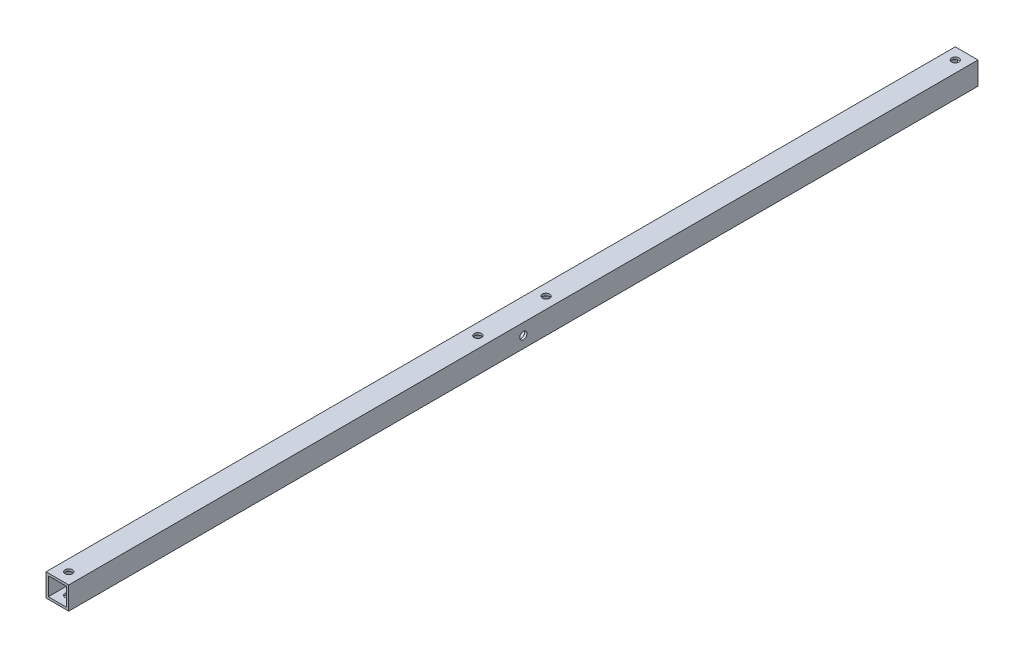
SolidWorks part; units mm, degrees
ref_plane "正面" through (0, 0, 0) normal (0, 0, 1) x (1, 0, 0)
ref_plane "平面" through (0, 0, 0) normal (0, 1, 0) x (1, 0, 0)
ref_plane "右側面" through (0, 0, 0) normal (1, 0, 0) x (0, 0, -1)
sketch "ｽｹｯﾁ1" plane through (0, 0, 0) normal (0, 0, 1) x (1, 0, 0)
  line L0 (-4, 4) -> (-4, -4)
  line L1 (-5, 5) -> (5, 5)
  line L2 (-5, 5) -> (-5, -5)
  line L3 (-5, -5) -> (5, -5)
  line L4 (5, 5) -> (5, -5)
  line L5 (-5, 5) -> (5, -5) construction
  line L6 (-5, -5) -> (5, 5) construction
  line L7 (-4, -4) -> (4, -4)
  line L8 (4, 4) -> (4, -4)
  line L9 (-4, 4) -> (4, 4)
  point P0 (0, 0)
  dimension "D1" = 10
  dimension "D2" = 10
  dimension "D3" = 1
extrude "ﾎﾞｽ - 押し出し1" add sketch "ｽｹｯﾁ1" along normal blind 399.7114
sketch "ｽｹｯﾁ2" plane through (0, 5, 0) normal (0, 1, 0) x (1, 0, 0)
  line L0 (5, -399.7114) -> (-5, -399.7114) construction
  line L1 (5, 0) -> (-5, 0) construction
  line L2 (-5, -399.7114) -> (-5, 0) construction
  circle A0 centre (0, -5) radius 1.6
  circle A1 centre (0, -394.7114) radius 1.6
  circle A2 centre (0, -184.8557) radius 1.6
  circle A3 centre (0, -214.8557) radius 1.6
  point P14 (-5, -199.8557)
  dimension "D1" = 5
  dimension "D2" = 3.2
  dimension "D3" = 5
  dimension "D4" = 3.2
  dimension "D5" = 15
  dimension "D6" = 15
  dimension "D7" = 3.2
  dimension "D8" = 3.2
extrude "ｶｯﾄ - 押し出し1" cut sketch "ｽｹｯﾁ2" against normal blind 408.3717
sketch "ｽｹｯﾁ3" plane through (-5, 0, 0) normal (-1, 0, 0) x (0, 0, 1)
  circle A0 centre (199.8557, 0) radius 1.6
  dimension "D1" = 3.2
extrude "ｶｯﾄ - 押し出し2" cut sketch "ｽｹｯﾁ3" against normal blind 10
